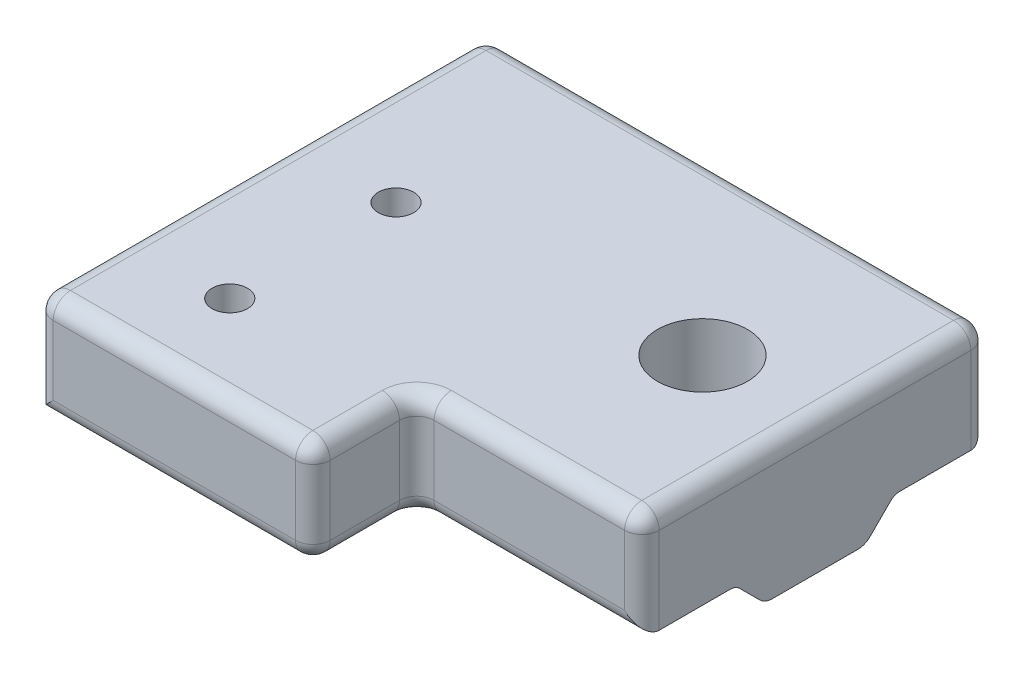
SolidWorks part; units mm, degrees
ref_plane "Front Plane" through (0, 0, 0) normal (0, 0, 1) x (1, 0, 0)
ref_plane "Top Plane" through (0, 0, 0) normal (0, 1, 0) x (1, 0, 0)
ref_plane "Right Plane" through (0, 0, 0) normal (1, 0, 0) x (0, 0, -1)
sketch "Sketch1" plane through (32.3643, 0, 0) normal (1, 0, 0) x (0, 0, -1)
  line L0 (-10.7659, 34.0751) -> (-4.9859, 34.0751)
  line L1 (-17.8759, 35.7651) -> (2.1241, 35.7651)
  line L2 (-17.8759, 35.7651) -> (-17.8759, 41.7651)
  line L3 (-17.8759, 41.7651) -> (2.1241, 41.7651)
  line L4 (2.1241, 35.7651) -> (2.1241, 41.7651)
  line L52 (-5.5365, 22.3651) -> (-2.3759, 19.2044)
  line L53 (-2.3759, 19.2044) -> (-2.3759, 17.5651)
  line L54 (-2.3759, 17.5651) -> (-4.9859, 17.5651)
  line L55 (-4.9859, 17.5651) -> (-4.9859, 17.4551)
  line L56 (-4.9859, 17.4551) -> (-3.5273, 15.9964)
  line L57 (-2.9686, 15.7651) -> (0.6241, 15.7651)
  line L58 (2.1241, 17.2651) -> (2.1241, 20.8578)
  line L59 (1.8927, 21.4164) -> (0.4341, 22.8751)
  line L60 (0.4341, 22.8751) -> (0.3241, 22.8751)
  line L61 (0.3241, 22.8751) -> (0.3241, 20.2651)
  line L62 (0.3241, 20.2651) -> (-1.3152, 20.2651)
  line L63 (-1.3152, 20.2651) -> (-4.4759, 23.4257)
  line L64 (-4.4759, 23.4257) -> (-4.4759, 28.1044)
  line L65 (-4.4759, 28.1044) -> (-1.3152, 31.2651)
  line L66 (-1.3152, 31.2651) -> (0.3241, 31.2651)
  line L67 (0.3241, 31.2651) -> (0.3241, 28.6551)
  line L68 (0.3241, 28.6551) -> (0.4341, 28.6551)
  line L69 (0.4341, 28.6551) -> (1.8927, 30.1137)
  line L70 (2.1241, 30.6723) -> (2.1241, 34.2651)
  line L71 (0.6241, 35.7651) -> (-2.9686, 35.7651)
  line L72 (-3.5273, 35.5337) -> (-4.9859, 34.0751)
  line L73 (-4.9859, 34.0751) -> (-4.9859, 33.9651)
  line L74 (-4.9859, 33.9651) -> (-2.3759, 33.9651)
  line L75 (-2.3759, 33.9651) -> (-2.3759, 32.3257)
  line L76 (-2.3759, 32.3257) -> (-5.5365, 29.1651)
  line L77 (-5.5365, 29.1651) -> (-10.2152, 29.1651)
  line L78 (-10.2152, 29.1651) -> (-13.3759, 32.3257)
  line L79 (-13.3759, 32.3257) -> (-13.3759, 33.9651)
  line L80 (-13.3759, 33.9651) -> (-10.7659, 33.9651)
  line L81 (-10.7659, 33.9651) -> (-10.7659, 34.0751)
  line L82 (-10.7659, 34.0751) -> (-12.2245, 35.5337)
  line L83 (-12.7831, 35.7651) -> (-16.3759, 35.7651)
  line L84 (-17.8759, 34.2651) -> (-17.8759, 30.6723)
  line L85 (-17.6445, 30.1137) -> (-16.1859, 28.6551)
  line L86 (-16.1859, 28.6551) -> (-16.0759, 28.6551)
  line L87 (-16.0759, 28.6551) -> (-16.0759, 31.2651)
  line L88 (-16.0759, 31.2651) -> (-14.4365, 31.2651)
  line L89 (-14.4365, 31.2651) -> (-11.2759, 28.1044)
  line L90 (-11.2759, 28.1044) -> (-11.2759, 23.4257)
  line L91 (-11.2759, 23.4257) -> (-14.4365, 20.2651)
  line L92 (-14.4365, 20.2651) -> (-16.0759, 20.2651)
  line L93 (-16.0759, 20.2651) -> (-16.0759, 22.8751)
  line L94 (-16.0759, 22.8751) -> (-16.1859, 22.8751)
  line L95 (-16.1859, 22.8751) -> (-17.6445, 21.4164)
  line L96 (-17.8759, 20.8578) -> (-17.8759, 17.2651)
  line L97 (-16.3759, 15.7651) -> (-12.7831, 15.7651)
  line L98 (-12.2245, 15.9964) -> (-10.7659, 17.4551)
  line L99 (-10.7659, 17.4551) -> (-10.7659, 17.5651)
  line L100 (-10.7659, 17.5651) -> (-13.3759, 17.5651)
  line L101 (-13.3759, 17.5651) -> (-13.3759, 19.2044)
  line L102 (-13.3759, 19.2044) -> (-10.2152, 22.3651)
  line L103 (-10.2152, 22.3651) -> (-5.5365, 22.3651)
  line L104 (-5.5365, 22.3651) -> (-2.3759, 19.2044)
  line L105 (-2.3759, 19.2044) -> (-2.3759, 17.5651)
  line L106 (-2.3759, 17.5651) -> (-4.9859, 17.5651)
  line L107 (-4.9859, 17.5651) -> (-4.9859, 17.4551)
  line L108 (-4.9859, 17.4551) -> (-3.5273, 15.9964)
  line L109 (-2.9686, 15.7651) -> (0.6241, 15.7651)
  line L110 (2.1241, 17.2651) -> (2.1241, 20.8578)
  line L111 (1.8927, 21.4164) -> (0.4341, 22.8751)
  line L112 (0.4341, 22.8751) -> (0.3241, 22.8751)
  line L113 (0.3241, 22.8751) -> (0.3241, 20.2651)
  line L114 (0.3241, 20.2651) -> (-1.3152, 20.2651)
  line L115 (-1.3152, 20.2651) -> (-4.4759, 23.4257)
  line L116 (-4.4759, 23.4257) -> (-4.4759, 28.1044)
  line L117 (-4.4759, 28.1044) -> (-1.3152, 31.2651)
  line L118 (-1.3152, 31.2651) -> (0.3241, 31.2651)
  line L119 (0.3241, 31.2651) -> (0.3241, 28.6551)
  line L120 (0.3241, 28.6551) -> (0.4341, 28.6551)
  line L121 (0.4341, 28.6551) -> (1.8927, 30.1137)
  line L122 (2.1241, 30.6723) -> (2.1241, 34.2651)
  line L123 (0.6241, 35.7651) -> (-2.9686, 35.7651)
  line L124 (-3.5273, 35.5337) -> (-4.9859, 34.0751)
  line L125 (-4.9859, 34.0751) -> (-4.9859, 33.9651)
  line L126 (-4.9859, 33.9651) -> (-2.3759, 33.9651)
  line L127 (-2.3759, 33.9651) -> (-2.3759, 32.3257)
  line L128 (-2.3759, 32.3257) -> (-5.5365, 29.1651)
  line L129 (-5.5365, 29.1651) -> (-10.2152, 29.1651)
  line L130 (-10.2152, 29.1651) -> (-13.3759, 32.3257)
  line L131 (-13.3759, 32.3257) -> (-13.3759, 33.9651)
  line L132 (-13.3759, 33.9651) -> (-10.7659, 33.9651)
  line L133 (-10.7659, 33.9651) -> (-10.7659, 34.0751)
  line L134 (-10.7659, 34.0751) -> (-12.2245, 35.5337)
  line L135 (-12.7831, 35.7651) -> (-16.3759, 35.7651)
  line L136 (-17.8759, 34.2651) -> (-17.8759, 30.6723)
  line L137 (-17.6445, 30.1137) -> (-16.1859, 28.6551)
  line L138 (-16.1859, 28.6551) -> (-16.0759, 28.6551)
  line L139 (-16.0759, 28.6551) -> (-16.0759, 31.2651)
  line L140 (-16.0759, 31.2651) -> (-14.4365, 31.2651)
  line L141 (-14.4365, 31.2651) -> (-11.2759, 28.1044)
  line L142 (-11.2759, 28.1044) -> (-11.2759, 23.4257)
  line L143 (-11.2759, 23.4257) -> (-14.4365, 20.2651)
  line L144 (-14.4365, 20.2651) -> (-16.0759, 20.2651)
  line L145 (-16.0759, 20.2651) -> (-16.0759, 22.8751)
  line L146 (-16.0759, 22.8751) -> (-16.1859, 22.8751)
  line L147 (-16.1859, 22.8751) -> (-17.6445, 21.4164)
  line L148 (-17.8759, 20.8578) -> (-17.8759, 17.2651)
  line L149 (-16.3759, 15.7651) -> (-12.7831, 15.7651)
  line L150 (-12.2245, 15.9964) -> (-10.7659, 17.4551)
  line L151 (-10.7659, 17.4551) -> (-10.7659, 17.5651)
  line L152 (-10.7659, 17.5651) -> (-13.3759, 17.5651)
  line L153 (-13.3759, 17.5651) -> (-13.3759, 19.2044)
  line L154 (-13.3759, 19.2044) -> (-10.2152, 22.3651)
  line L155 (-10.2152, 22.3651) -> (-5.5365, 22.3651)
  arc A12 (-3.5273, 15.9964) -> (-2.9686, 15.7651) centre (-2.9686, 16.5551) ccw
  arc A13 (0.6241, 15.7651) -> (2.1241, 17.2651) centre (0.6241, 17.2651) ccw
  arc A14 (2.1241, 20.8578) -> (1.8927, 21.4164) centre (1.3341, 20.8578) ccw
  arc A15 (1.8927, 30.1137) -> (2.1241, 30.6723) centre (1.3341, 30.6723) ccw
  arc A16 (2.1241, 34.2651) -> (0.6241, 35.7651) centre (0.6241, 34.2651) ccw
  arc A17 (-2.9686, 35.7651) -> (-3.5273, 35.5337) centre (-2.9686, 34.9751) ccw
  arc A18 (-12.2245, 35.5337) -> (-12.7831, 35.7651) centre (-12.7831, 34.9751) ccw
  arc A19 (-16.3759, 35.7651) -> (-17.8759, 34.2651) centre (-16.3759, 34.2651) ccw
  arc A20 (-17.8759, 30.6723) -> (-17.6445, 30.1137) centre (-17.0859, 30.6723) ccw
  arc A21 (-17.6445, 21.4164) -> (-17.8759, 20.8578) centre (-17.0859, 20.8578) ccw
  arc A22 (-17.8759, 17.2651) -> (-16.3759, 15.7651) centre (-16.3759, 17.2651) ccw
  arc A23 (-12.7831, 15.7651) -> (-12.2245, 15.9964) centre (-12.7831, 16.5551) ccw
  arc A24 (-3.5273, 15.9964) -> (-2.9686, 15.7651) centre (-2.9686, 16.5551) ccw
  arc A25 (0.6241, 15.7651) -> (2.1241, 17.2651) centre (0.6241, 17.2651) ccw
  arc A26 (2.1241, 20.8578) -> (1.8927, 21.4164) centre (1.3341, 20.8578) ccw
  arc A27 (1.8927, 30.1137) -> (2.1241, 30.6723) centre (1.3341, 30.6723) ccw
  arc A28 (2.1241, 34.2651) -> (0.6241, 35.7651) centre (0.6241, 34.2651) ccw
  arc A29 (-2.9686, 35.7651) -> (-3.5273, 35.5337) centre (-2.9686, 34.9751) ccw
  arc A30 (-12.2245, 35.5337) -> (-12.7831, 35.7651) centre (-12.7831, 34.9751) ccw
  arc A31 (-16.3759, 35.7651) -> (-17.8759, 34.2651) centre (-16.3759, 34.2651) ccw
  arc A32 (-17.8759, 30.6723) -> (-17.6445, 30.1137) centre (-17.0859, 30.6723) ccw
  arc A33 (-17.6445, 21.4164) -> (-17.8759, 20.8578) centre (-17.0859, 20.8578) ccw
  arc A34 (-17.8759, 17.2651) -> (-16.3759, 15.7651) centre (-16.3759, 17.2651) ccw
  arc A35 (-12.7831, 15.7651) -> (-12.2245, 15.9964) centre (-12.7831, 16.5551) ccw
  dimension "D2" = 6
  dimension "D1" = 0
extrude "Boss-Extrude1" add sketch "Sketch1" along normal blind 13 contours L1 L4 L3 L2 | A30 L134 L0 L124 A29 L1 region at (32.3643, 34.9853, 7.8759) region at (32.3643, 38.7651, 7.8759)
sketch "Sketch2" plane through (0, 34.0751, 0) normal (0, -1, 0) x (1, 0, 0)
  line L0 (45.3643, 4.9859) -> (32.3643, 10.7659) construction
  line L1 (32.3643, 10.7659) -> (32.3643, 4.9859) construction
  line L2 (32.3643, 4.9859) -> (45.3643, 10.7659) construction
  circle A0 centre (38.8643, 7.8759) radius 2.6
  dimension "D1" = 5.2
extrude "Cut-Extrude1" cut sketch "Sketch2" against normal up to next
sketch "Sketch5" plane through (32.3643, 0, 0) normal (-1, 0, 0) x (0, 0, 1)
  line L8 (12.7831, 35.7651) -> (17.8759, 35.7651)
  line L9 (17.8759, 35.7651) -> (17.8759, 41.7651)
  line L10 (17.8759, 41.7651) -> (-2.1241, 41.7651)
  line L11 (-2.1241, 41.7651) -> (-2.1241, 35.7651)
  line L12 (-2.1241, 35.7651) -> (2.9686, 35.7651)
  line L13 (3.5273, 35.5337) -> (4.9859, 34.0751)
  line L14 (4.9859, 34.0751) -> (10.7659, 34.0751)
  line L15 (10.7659, 34.0751) -> (12.2245, 35.5337)
  line L16 (12.7831, 35.7651) -> (17.8759, 35.7651)
  line L17 (17.8759, 35.7651) -> (17.8759, 41.7651)
  line L18 (17.8759, 41.7651) -> (-2.1241, 41.7651)
  line L19 (-2.1241, 41.7651) -> (-2.1241, 35.7651)
  line L20 (-2.1241, 35.7651) -> (2.9686, 35.7651)
  line L21 (3.5273, 35.5337) -> (4.9859, 34.0751)
  line L22 (4.9859, 34.0751) -> (10.7659, 34.0751)
  line L23 (10.7659, 34.0751) -> (12.2245, 35.5337)
  arc A2 (3.5273, 35.5337) -> (2.9686, 35.7651) centre (2.9686, 34.9751) ccw
  arc A3 (12.7831, 35.7651) -> (12.2245, 35.5337) centre (12.7831, 34.9751) ccw
  arc A4 (3.5273, 35.5337) -> (2.9686, 35.7651) centre (2.9686, 34.9751) ccw
  arc A5 (12.7831, 35.7651) -> (12.2245, 35.5337) centre (12.7831, 34.9751) ccw
  dimension "D1" = 0
extrude "Boss-Extrude3" add sketch "Sketch5" along normal blind 16
sketch "Sketch6" plane through (0, 0, 17.8759) normal (0, 0, 1) x (1, 0, 0)
  line L0 (45.3643, 35.7651) -> (16.3643, 35.7651) construction
  line L1 (16.3643, 41.7651) -> (32.3643, 41.7651)
  line L2 (16.3643, 41.7651) -> (16.3643, 35.7651)
  line L3 (16.3643, 35.7651) -> (32.3643, 35.7651)
  line L4 (32.3643, 41.7651) -> (32.3643, 35.7651)
  dimension "D1" = 16
extrude "Boss-Extrude4" add sketch "Sketch6" along normal blind 6
sketch "Sketch7" plane through (0, 41.7651, 0) normal (0, 1, 0) x (1, 0, 0)
  line L0 (16.3643, -23.8759) -> (16.3643, 2.1241) construction
  line L1 (32.3643, -23.8759) -> (16.3643, -23.8759) construction
  circle A0 centre (22.3643, -9.0759) radius 1.025
  circle A1 centre (22.3643, -18.6759) radius 1.025
  dimension "D1" = 6
  dimension "D5" = 2.05
  dimension "D6" = 2.05
  dimension "D2" = 6
  dimension "D3" = 9.6
  dimension "D4" = 5.2
extrude "Cut-Extrude3" cut sketch "Sketch7" against normal blind 6
fillet "Fillet3" radius 1 18 edges at (45.3643, 38.7651, 17.8759) (32.3643, 38.7651, 23.8759) (16.3643, 38.7651, 23.8759) (24.3643, 35.7651, 23.8759) (30.8643, 34.0751, 10.7659) (30.8643, 34.0751, 4.9859) (30.8643, 35.7651, -2.1241) (45.3643, 38.7651, -2.1241) (16.3643, 38.7651, -2.1241) (30.8643, 41.7651, -2.1241) (45.3643, 41.7651, 7.8759) (16.3643, 41.7651, 10.8759) (24.3643, 41.7651, 23.8759)
